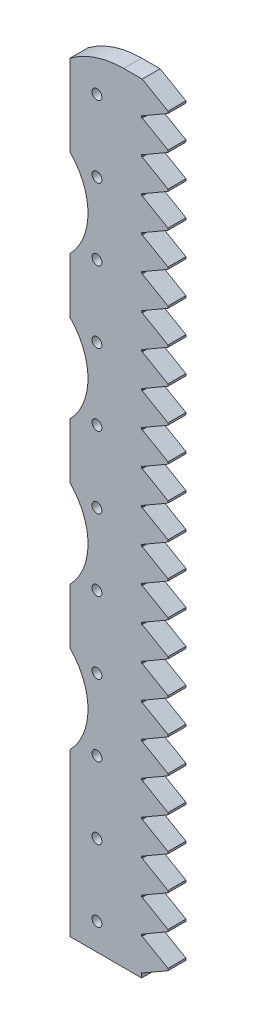
SolidWorks part; units mm, degrees
ref_plane "Front Plane" through (0, 0, 0) normal (0, 0, 1) x (1, 0, 0)
ref_plane "Top Plane" through (0, 0, 0) normal (0, 1, 0) x (1, 0, 0)
ref_plane "Right Plane" through (0, 0, 0) normal (1, 0, 0) x (0, 0, -1)
sketch "Sketch1" plane through (0, 0, 0) normal (0, 0, 1) x (1, 0, 0)
  line L1 (0, 0) -> (-25.4, 0)
  line L2 (0, 0) -> (0, 276.225)
  line L3 (0, 276.225) -> (-25.4, 276.225)
  line L4 (-25.4, 0) -> (-25.4, 276.225)
  dimension "D1" = 25.4
  dimension "D2" = 276.225
extrude "Boss-Extrude1" add sketch "Sketch1" along normal blind 6.35
sketch "Sketch2" plane through (0, 0, 6.35) normal (0, 0, 1) x (1, 0, 0)
  line L0 (0, 276.225) -> (-25.4, 276.225) construction
  line L1 (-6.35, 276.225) -> (-25.4, 276.225)
  line L2 (-25.4, 276.225) -> (-25.4, 269.875)
  line L3 (-25.4, 276.225) -> (-25.4, 0) construction
  arc A0 (-6.35, 276.225) -> (-25.4, 269.875) centre (-6.35, 244.475) ccw
  dimension "D1" = 31.75
  dimension "D2" = 6.35
extrude "Cut-Extrude1" cut sketch "Sketch2" against normal through all contours L1 L2 A0
sketch "Sketch3" plane through (0, 0, 6.35) normal (0, 0, 1) x (1, 0, 0)
  line L0 (0, 276.225) -> (-6.35, 276.225) construction
  line L1 (0, 0) -> (0, 276.225) construction
  circle A0 centre (-15.875, 263.525) radius 1.75
  dimension "D1" = 3.5
  dimension "D2" = 12.7
  dimension "D3" = 15.875
extrude "Cut-Extrude2" cut sketch "Sketch3" against normal through all
pattern_linear "LPattern1" count 11 spacing 25.4 along (0, -1, 0) of "Cut-Extrude2"
sketch "Sketch4" plane through (0, 0, 6.35) normal (0, 0, 1) x (1, 0, 0)
  line L0 (-15.875, 238.125) -> (-15.875, 212.725) construction
  line L1 (-15.875, 225.425) -> (-41.275, 225.425) construction
  circle A0 centre (-41.275, 225.425) radius 22.225
  dimension "D2" = 44.45
  dimension "D1" = 25.4
extrude "Cut-Extrude3" cut sketch "Sketch4" against normal through all
pattern_linear "LPattern2" count 4 spacing 50.8 along (0, -1, 0) of "Cut-Extrude3"
sketch "Sketch5" plane through (0, 0, 6.35) normal (0, 0, 1) x (1, 0, 0)
  line L0 (0.1905, 276.225) -> (9.3345, 270.9457)
  line L1 (9.3345, 270.9457) -> (9.3345, 270.2403)
  line L2 (9.3345, 270.2403) -> (0.1905, 264.961)
  line L3 (0, 276.225) -> (0, 264.961)
  line L4 (0.1905, 264.961) -> (0.1905, 276.225) construction
  line L5 (4.7625, 273.5854) -> (4.7625, 267.6006) construction
  line L6 (9.3345, 270.593) -> (0.1905, 270.593) construction
  line L7 (0.1905, 276.225) -> (0, 276.225)
  line L8 (0, 0) -> (0, 276.225) construction
  line L9 (0, 264.961) -> (0.1905, 264.961)
  point P11 (4.7625, 270.593)
  point P12 (4.7625, 270.593)
  dimension "D1" = 5.9847
  dimension "D2" = 60
  dimension "D3" = 4.572
  dimension "D4" = 4.7625
extrude "Boss-Extrude2" add sketch "Sketch5" against normal through all
pattern_linear "LPattern3" count 23 spacing 11.9695 along (0, -1, 0) of "Boss-Extrude2"
